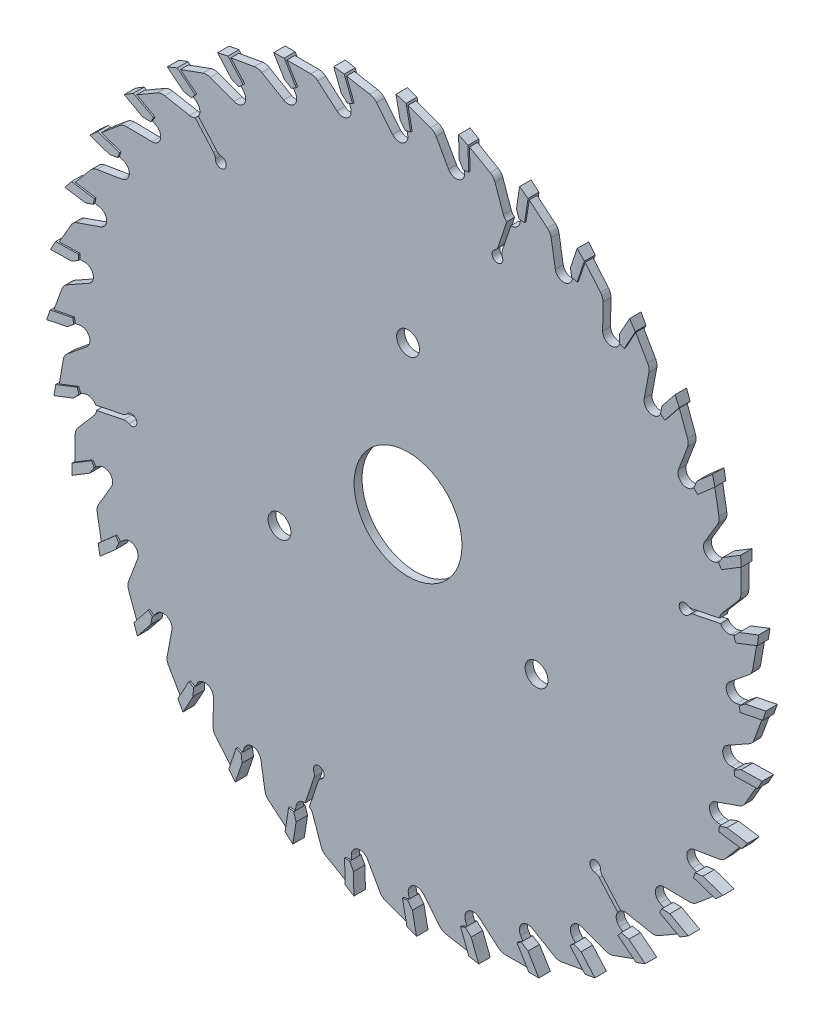
SolidWorks part; units mm, degrees
material "Stal węglowa"
ref_plane "Płaszczyzna przednia" through (0, 0, 0) normal (0, 0, 1) x (1, 0, 0)
ref_plane "Płaszczyzna górna" through (0, 0, 0) normal (0, 1, 0) x (1, 0, 0)
ref_plane "Płaszczyzna prawa" through (0, 0, 0) normal (1, 0, 0) x (0, 0, -1)
sketch "Szkic1" plane through (0, 0, 0) normal (0, 0, 1) x (1, 0, 0)
  circle A0 centre (0, 0) radius 15
  circle A1 centre (0, 0) radius 98.5
  dimension "D1" = 30
  dimension "D2" = 197
extrude "Dodanie-wyciągnięcie1" add sketch "Szkic1" along normal mid plane 2.2
sketch "Szkic2" plane through (0, 0, 1.1) normal (0, 0, 1) x (1, 0, 0)
  line L0 (0, 0) -> (0, 98.5) construction
  line L1 (0, 98.5) -> (1.1365, 92.8124)
  line L2 (1.1365, 92.8124) -> (-0.3344, 92.5185)
  line L3 (-0.3344, 92.5185) -> (-1.5273, 98.4882)
  circle A0 centre (0, 0) radius 98.5 construction
  arc A1 (0, 98.5) -> (-1.5273, 98.4882) centre (0, 0) ccw
  dimension "D1" = 1.5
  dimension "D2" = 5.8
  dimension "D3" = 11.3
extrude "Wytnij-wyciągnięcie1" cut sketch "Szkic2" against normal through all
sketch "Szkic3" plane through (0, 0, 1.1) normal (0, 0, 1) x (1, 0, 0)
  line L0 (-0.3344, 92.5185) -> (0.4688, 88.4988) construction
  line L1 (-1.5273, 98.4882) -> (-0.3344, 92.5185) construction
  line L2 (-1.5273, 98.4882) -> (-0.0984, 91.3372)
  line L3 (-4.3091, 89.3468) -> (-11.2713, 97.853)
  circle A0 centre (0, 0) radius 88.5 construction
  arc A1 (-1.5273, 98.4882) -> (0, 98.5) centre (0, 0) ccw construction
  circle A2 centre (-2.4519, 90.8669) radius 2.4 construction
  arc A3 (-1.5273, 98.4882) -> (-11.2713, 97.853) centre (0, 0) ccw
  arc A4 (-4.3091, 89.3468) -> (-0.0984, 91.3372) centre (-2.4519, 90.8669) ccw
  dimension "D1" = 10
  dimension "D3" = 2.4
  dimension "D2" = 28
extrude "Wytnij-wyciągnięcie2" cut sketch "Szkic3" against normal through all
ref_axis "Oś1" through (0, 0, 14.5024) along (0, 0, -1)
pattern_circular "Szyk kołowy2" count 36 over 360 about axis through (0, 0, 14.5024) along (0, 0, -1) of "Wytnij-wyciągnięcie1", "Wytnij-wyciągnięcie2"
sketch "Szkic4" plane through (0, 0, 1.1) normal (0, 0, 1) x (1, 0, 0)
  line L0 (0, 0) -> (-17.1043, 97.0036) construction
  line L1 (-17.1043, 97.0036) -> (-11.3994, 98.0095)
  line L2 (-11.2713, 97.853) -> (-4.3091, 89.3468) construction
  line L3 (-17.1043, 97.0036) -> (-9.475, 95.6583)
  line L4 (-9.475, 95.6583) -> (-11.3994, 98.0095)
  dimension "D1" = 20
extrude "Wytnij-wyciągnięcie3" cut sketch "Szkic4" against normal through all
sketch "Szkic5" plane through (0, 0, 1.1) normal (0, 0, 1) x (1, 0, 0)
  line L0 (-10.5708, 95.8515) -> (-9.475, 95.6583)
  line L1 (-9.475, 95.6583) -> (-8.7702, 94.7972)
  line L2 (-9.475, 95.6583) -> (-4.3091, 89.3468) construction
  line L3 (-17.1043, 97.0036) -> (-9.475, 95.6583) construction
  arc A0 (-8.7702, 94.7972) -> (-10.5708, 95.8515) centre (-11.0917, 92.8971) ccw
  dimension "D1" = 3
extrude "Wytnij-wyciągnięcie4" cut sketch "Szkic5" against normal through all
sketch "Szkic7" plane through (0, 0, 0) normal (0, 0, 1) x (1, 0, 0)
  line L0 (-0.1186, 99.0933) -> (1.1365, 92.8124)
  line L1 (1.1365, 92.8124) -> (-0.3344, 92.5185)
  line L2 (-0.3344, 92.5185) -> (-1.7069, 94.2838)
  line L3 (-1.7069, 94.2838) -> (-2.8492, 100)
  line L4 (-2.8492, 100) -> (-0.1186, 99.0933)
  line L5 (-2.8492, 100) -> (-0.3142, 100.0722) construction
  line L6 (1.1365, 92.8124) -> (0, 98.5) construction
  line L7 (-0.3344, 92.5185) -> (1.1365, 92.8124) construction
  line L8 (-2.8492, 100) -> (2.8492, -100) construction
  dimension "D1" = 200
  dimension "D2" = 2.5
  dimension "D3" = 1.5
  dimension "D4" = 2
  dimension "D5" = 20
extrude "Dodanie-wyciągnięcie2" add sketch "Szkic7" along normal mid plane 3.2
sketch "Szkic9" plane through (-17.7901, 89.0305, 0) normal (0.1959, -0.9806, 0) x (0.9806, 0.1959, 0)
  line L0 (16.8007, 1.6) -> (19.3007, 1.5127)
  line L1 (19.3007, 1.5127) -> (19.3007, 1.6)
  line L3 (19.3007, 1.6) -> (16.8007, 1.6)
  line L7 (16.8007, -1.6) -> (19.3007, -1.6)
  line L10 (19.3007, -1.6) -> (19.3007, -1.5127)
  line L11 (19.3007, -1.5127) -> (16.8007, -1.6)
  line L13 (17.8007, -1.6) -> (19.3007, -1.6) construction
  line L14 (19.3007, -1.1) -> (19.3007, -1.6) construction
  line L15 (19.3007, 1.6) -> (19.3007, 1.1) construction
  line L16 (17.8007, 1.6) -> (19.3007, 1.6) construction
  dimension "D1" = 2
extrude "Wytnij-wyciągnięcie6" cut sketch "Szkic9" against normal blind 15
pattern_circular "Szyk kołowy3" count 36 over 360 about axis through (0, 0, 14.5024) along (0, 0, -1) of "Wytnij-wyciągnięcie3", "Wytnij-wyciągnięcie4", "Dodanie-wyciągnięcie2", "Wytnij-wyciągnięcie6"
sketch "Szkic6" plane through (0, 0, 1.1) normal (0, 0, 1) x (1, 0, 0)
  line L0 (-60.2864, 68.0321) -> (0, 0) construction
  line L1 (-59.1942, 65.895) -> (-58.2961, 66.6908)
  line L2 (-58.2961, 66.6908) -> (-53.1674, 60.9031)
  line L3 (-59.1942, 65.895) -> (-54.0655, 60.1073)
  arc A0 (-60.732, 65.6738) -> (-58.7858, 69.9051) centre (-60.2864, 68.0321) ccw construction
  arc A1 (-53.5624, 58.7641) -> (-51.8945, 60.2421) centre (-52.0625, 58.7516) ccw
  arc A2 (-53.1674, 60.9031) -> (-51.8945, 60.2421) centre (-51.6705, 62.2296) ccw
  arc A3 (-54.0655, 60.1073) -> (-53.5624, 58.7641) centre (-55.5624, 58.7808) cw
  point P4 (-58.6946, 66.2359)
  point P5 (-52.0625, 58.7516)
  point P16 (-52.5252, 60.1784)
  point P19 (-53.4233, 59.3826)
  dimension "D2" = 2
  dimension "D4" = 1.5
  dimension "D1" = 10
  dimension "D3" = 1.2
extrude "Wytnij-wyciągnięcie5" cut sketch "Szkic6" against normal through all
pattern_circular "Szyk kołowy4" count 6 over 360 about axis through (0, 0, 14.5024) along (0, 0, -1) of "Wytnij-wyciągnięcie5"
sketch "Sketch1" plane through (0, 0, 1.1) normal (0, 0, 1) x (1, 0, 0)
  line L0 (0, 0) -> (0, 41.275) construction
  circle A0 centre (0, 41.275) radius 3.175
  circle A1 centre (35.7452, -20.6375) radius 3.175
  circle A2 centre (-35.7452, -20.6375) radius 3.175
  point P4 (35.1562, -25.5317)
  point P5 (0, 0)
  point P11 (0, 0)
  dimension "D1" = 6.35
  dimension "D2" = 41.275
  dimension "D3" = 3
extrude "Cut-Extrude1" cut sketch "Sketch1" against normal up to next
